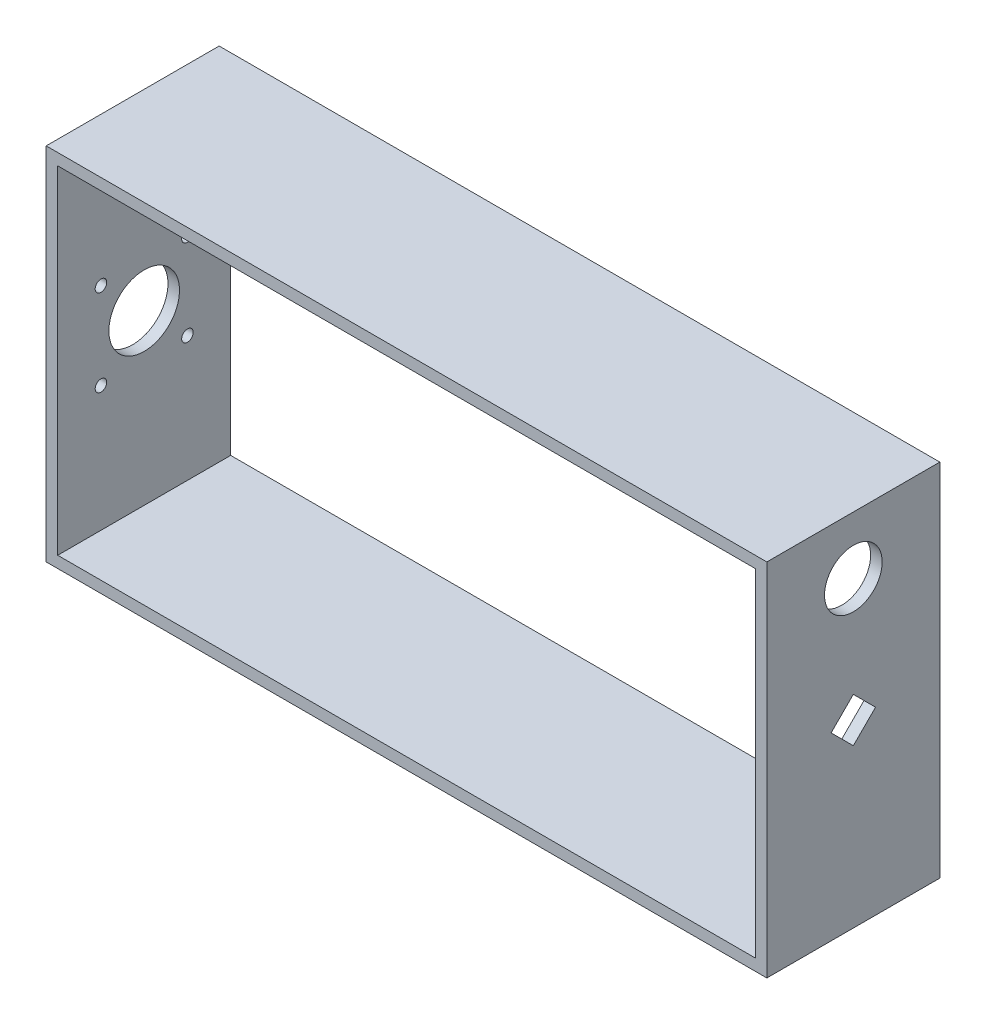
SolidWorks part; units mm, degrees
ref_plane "Ebene vorne" through (0, 0, 0) normal (0, 0, 1) x (1, 0, 0)
ref_plane "Ebene oben" through (0, 0, 0) normal (0, 1, 0) x (1, 0, 0)
ref_plane "Ebene rechts" through (0, 0, 0) normal (1, 0, 0) x (0, 0, -1)
sketch "Skizze1" plane through (0, 0, 0) normal (0, 0, 1) x (1, 0, 0)
  line L1 (0, 125) -> (250, 125)
  line L2 (0, 125) -> (0, 0)
  line L3 (0, 0) -> (250, 0)
  line L4 (250, 125) -> (250, 0)
  line L5 (246, 121) -> (4, 121)
  line L6 (246, 121) -> (246, 4)
  line L7 (246, 4) -> (4, 4)
  line L8 (4, 121) -> (4, 4)
  dimension "D1" = 250
  dimension "D2" = 125
  dimension "D3" = 4
  dimension "D4" = 4
  dimension "D5" = 4
  dimension "D6" = 4
extrude "Aufsatz-Linear austragen1" add sketch "Skizze1" along normal blind 60
sketch "Skizze2" plane through (0, 0, 0) normal (-1, 0, 0) x (0, 0, 1)
  line L0 (0, 62.5) -> (60, 62.5) construction
  line L1 (30, 125) -> (30, 0) construction
  line L2 (60, 125) -> (0, 125) construction
  line L3 (60, 0) -> (0, 0) construction
  line L4 (0, 125) -> (0, 0) construction
  line L5 (60, 125) -> (60, 0) construction
  line L6 (15, 77.5) -> (45, 77.5) construction
  line L7 (45, 77.5) -> (45, 47.5) construction
  line L8 (45, 47.5) -> (15, 47.5) construction
  line L9 (15, 47.5) -> (15, 77.5) construction
  circle A0 centre (30, 62.5) radius 12.25
  circle A1 centre (15, 77.5) radius 2
  circle A2 centre (45, 77.5) radius 2
  circle A3 centre (45, 47.5) radius 2
  circle A4 centre (15, 47.5) radius 2
  point P17 (30, 62.5)
  point P21 (30, 77.5)
  point P22 (53.5816, 62.5)
  point P24 (15, 62.5)
  dimension "D1" = 30
  dimension "D2" = 30
extrude "Schnitt-Linear austragen1" cut sketch "Skizze2" against normal blind 10
sketch "Skizze8" plane through (250, 0, 0) normal (1, 0, 0) x (0, 0, -1)
  line L0 (-60, 62.5) -> (0, 62.5) construction
  line L1 (-60, 0) -> (-60, 125) construction
  line L2 (0, 0) -> (0, 125) construction
  line L3 (-30, 125) -> (-30, 0) construction
  line L4 (-60, 125) -> (0, 125) construction
  line L5 (-60, 0) -> (0, 0) construction
  line L6 (-30, 70.2075) -> (-37.7075, 62.5)
  line L11 (-30, 70.2075) -> (-22.2925, 62.5)
  line L12 (-37.7075, 62.5) -> (-30, 54.7925)
  line L13 (-22.2925, 62.5) -> (-30, 54.7925)
  line L14 (-30, 70.2075) -> (-30, 54.7925) construction
  line L15 (-37.7075, 62.5) -> (-22.2925, 62.5) construction
  circle A0 centre (-30, 105) radius 10
  point P13 (-30, 62.5)
  dimension "D3" = 20
  dimension "D4" = 20
  dimension "D1" = 10.9
  dimension "D2" = 10.9
  dimension "D5" = 30
extrude "Schnitt-Linear austragen6" cut sketch "Skizze8" against normal blind 12
sketch "Skizze9" plane through (250, 0, 0) normal (1, 0, 0) x (0, 0, -1)
